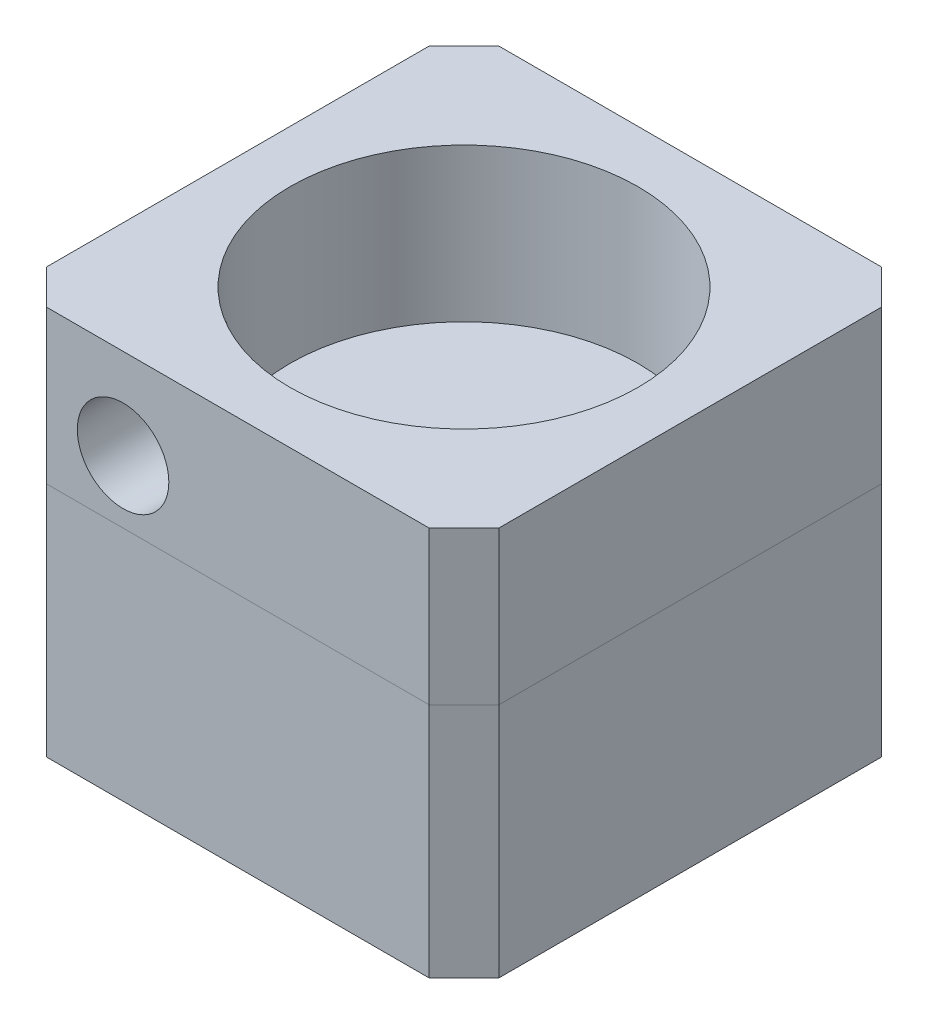
SolidWorks part; units mm, degrees
ref_plane "Front Plane" through (0, 0, 0) normal (0, 0, 1) x (1, 0, 0)
ref_plane "Top Plane" through (0, 0, 0) normal (0, 1, 0) x (1, 0, 0)
ref_plane "Right Plane" through (0, 0, 0) normal (1, 0, 0) x (0, 0, -1)
sketch "Sketch1" plane through (0, 0, 0) normal (0, 1, 0) x (1, 0, 0)
  line L1 (-32.5, -32.5) -> (32.5, -32.5)
  line L2 (-32.5, -32.5) -> (-32.5, 32.5)
  line L3 (-32.5, 32.5) -> (32.5, 32.5)
  line L4 (32.5, -32.5) -> (32.5, 32.5)
  line L5 (0, 32.5) -> (0, -32.5) construction
  line L6 (-32.5, 0) -> (32.5, 0) construction
  circle A0 centre (0, 0) radius 25
  circle A1 centre (0, 0) radius 6.5785
  circle A2 centre (-25.5, 25.5) radius 3
  circle A3 centre (25.5, 25.5) radius 3
  circle A4 centre (25.5, -25.5) radius 3
  circle A5 centre (-25.5, -25.5) radius 3
  circle A6 centre (-18.5, 26.5) radius 2
  circle A7 centre (18.5, 26.5) radius 2
  circle A8 centre (18.5, -26.5) radius 2
  circle A9 centre (-18.5, -26.5) radius 2
  dimension "D3" = 50
  dimension "D4" = 13.157
  dimension "D7" = 6
  dimension "D10" = 4
  dimension "D1" = 65
  dimension "D2" = 65
  dimension "D5" = 51
  dimension "D6" = 51
  dimension "D8" = 37
  dimension "D9" = 53
extrude "Boss-Extrude1" add sketch "Sketch1" along normal blind 34 contours L4 L3 L2 L1
chamfer "Chamfer1" distance 5 angle 45 4 edges at (-32.5, 17, -32.5) (32.5, 17, -32.5) (32.5, 17, 32.5) (-32.5, 17, 32.5)
sketch "Sketch2" plane through (0, 34, 0) normal (0, 1, 0) x (1, 0, 0)
  line L8 (27.5, 32.5) -> (-27.5, 32.5)
  line L9 (-27.5, 32.5) -> (-32.5, 27.5)
  line L10 (-32.5, 27.5) -> (-32.5, -27.5)
  line L11 (-32.5, -27.5) -> (-27.5, -32.5)
  line L12 (-27.5, -32.5) -> (27.5, -32.5)
  line L13 (27.5, -32.5) -> (32.5, -27.5)
  line L14 (32.5, -27.5) -> (32.5, 27.5)
  line L15 (32.5, 27.5) -> (27.5, 32.5)
  line L16 (27.5, 32.5) -> (-27.5, 32.5)
  line L17 (-27.5, 32.5) -> (-32.5, 27.5)
  line L18 (-32.5, 27.5) -> (-32.5, -27.5)
  line L19 (-32.5, -27.5) -> (-27.5, -32.5)
  line L20 (-27.5, -32.5) -> (27.5, -32.5)
  line L21 (27.5, -32.5) -> (32.5, -27.5)
  line L22 (32.5, -27.5) -> (32.5, 27.5)
  line L23 (32.5, 27.5) -> (27.5, 32.5)
  dimension "D1" = 0
extrude "Boss-Extrude2" add sketch "Sketch2" along normal blind 22 separate body
sketch "Sketch3" plane through (0, 0, 32.5) normal (0, 0, 1) x (1, 0, 0)
  line L0 (-27.5, 34) -> (27.5, 34) construction
  line L1 (-32.5, 56) -> (-32.5, 34) construction
  circle A0 centre (-16.5, 43) radius 6.5785
  dimension "D1" = 13.157
  dimension "D2" = 9
  dimension "D3" = 16
extrude "Cut-Extrude1" cut sketch "Sketch3" against normal blind 20
extrude "Cut-Extrude2" cut sketch "Sketch1<3>" against normal blind 22 from surface contours A0 starting at face at (0, 56, 0)
sketch "Sketch1<3>" plane through (0, 0, 0) normal (0, 1, 0) x (1, 0, 0) same geometry as "Sketch1"
hole_wizard "M4x0.7 Tapped Hole1" positions "Sketch4" profile "Sketch5" tap size "M4x0.7" standard "ANSI Metric"
sketch "Sketch4" plane through (0, 0, 0) normal (0, -1, 0) x (-1, 0, 0)
  point P0 (-18.5, 26.5)
  point P3 (18.5, 26.5)
  point P6 (-18.5, -26.5)
  point P9 (18.5, -26.5)
sketch "Sketch5" plane through (18.5, 0, -26.5) normal (1, 0, 0) x (0, 0, -1)
  line L0 (0, 0) -> (0, 11.0914)
  line L1 (0, 11.0914) -> (1.65, 10.1)
  line L2 (1.65, 10.1) -> (1.65, 0)
  line L5 (1.65, 0) -> (0, 0)
  line L10 (0, 11.0914) -> (-1.65, 10.1) construction
  line L11 (0, -6.35) -> (0, 107.95) construction
  dimension "Tap Drill Dia." = 3.3
  dimension "Tap Drill Depth" = 10.1
  dimension "Drill Angle" = 118
cosmetic thread "Hole Thread1" parameters "D1"=8, "D2"=4
cosmetic thread "Hole Thread2" parameters "D1"=8, "D2"=4
cosmetic thread "Hole Thread3" parameters "D1"=8, "D2"=4
cosmetic thread "Hole Thread4" parameters "D1"=8, "D2"=4
equation "\"D2@Sketch1\"=\"D1@Sketch1\""
equation "\"D6@Sketch1\"=\"D5@Sketch1\""
